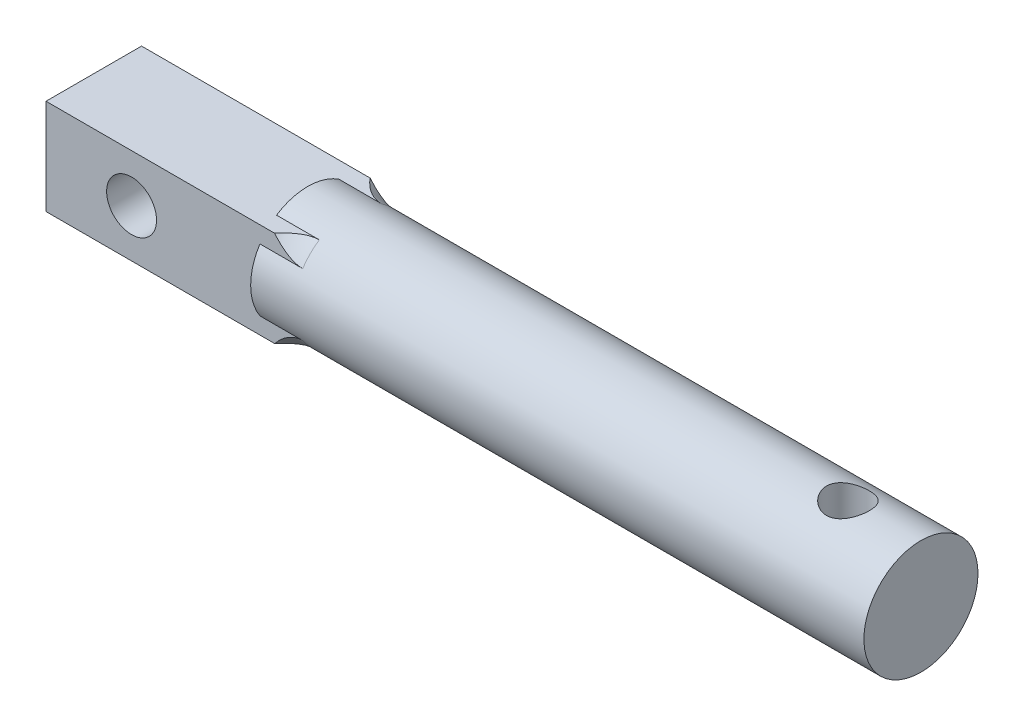
SolidWorks part; units mm, degrees
ref_plane "Plan de face" through (0, 0, 0) normal (1, 0, 0) x (0, 1, 0)
ref_plane "Plan de dessus" through (0, 0, 0) normal (0, 0, 1) x (0, 1, 0)
ref_plane "Plan de droite" through (0, 0, 0) normal (0, 1, 0) x (-1, 0, 0)
sketch "Esquisse1" plane through (0, 0, 0) normal (1, 0, 0) x (0, 1, 0)
  line L1 (-3.35, 3.35) -> (3.35, 3.35)
  line L2 (-3.35, 3.35) -> (-3.35, -3.35)
  line L3 (-3.35, -3.35) -> (3.35, -3.35)
  line L4 (3.35, 3.35) -> (3.35, -3.35)
  line L5 (-3.35, 3.35) -> (3.35, -3.35) construction
  line L6 (-3.35, -3.35) -> (3.35, 3.35) construction
  point P0 (0, 0)
  dimension "D1" = 6.7
  dimension "D2" = 6.7
extrude "Boss.-Extru.1" add sketch "Esquisse1" along normal blind 15
sketch "Esquisse2" plane through (15, 0, 0) normal (1, 0, 0) x (0, 1, 0)
  circle A0 centre (0, 0) radius 4
  dimension "D1" = 8
extrude "Boss.-Extru.2" add sketch "Esquisse2" along normal blind 43
sketch "Esquisse3" plane through (0, 0, 0) normal (0, 1, 0) x (-1, 0, 0)
  line L1 (-58, 4) -> (-58, -4) construction
  circle A0 centre (-52.88, 0) radius 1.5
  dimension "D1" = 3
  dimension "D2" = 5.12
extrude "Enlèv. mat.-Extru.1" cut sketch "Esquisse3" against normal through all both and the other way through all
fillet "Congé1" radius 3 4 edges at (15, 2.8284, -2.8284) (15, 2.8284, 2.8284) (15, -2.8284, 2.8284) (15, -2.8284, -2.8284)
sketch "Esquisse4" plane through (0, 0, 3.35) normal (0, 0, -1) x (-1, 0, 0)
  line L1 (0, -3.35) -> (0, 3.35) construction
  circle A0 centre (-6, 0) radius 1.75
  dimension "D1" = 3.5
  dimension "D2" = 6
extrude "Enlèv. mat.-Extru.2" cut sketch "Esquisse4" along normal through all and the other way through all
